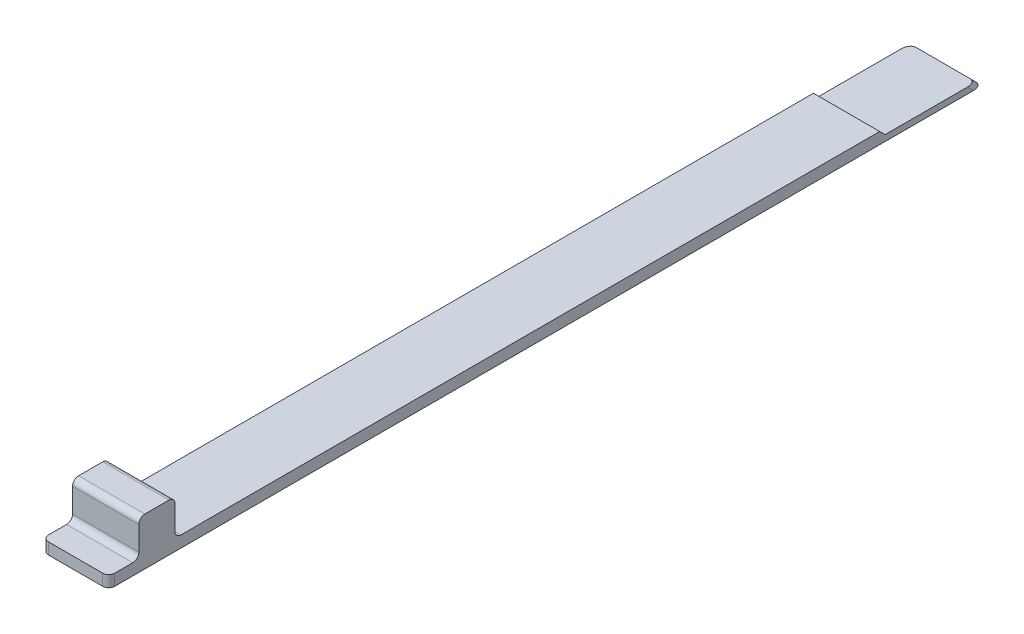
SolidWorks part; units mm, degrees
ref_plane "Front Plane" through (0, 0, 0) normal (0, 0, 1) x (1, 0, 0)
ref_plane "Top Plane" through (0, 0, 0) normal (0, 1, 0) x (1, 0, 0)
ref_plane "Right Plane" through (0, 0, 0) normal (1, 0, 0) x (0, 0, -1)
sketch "Szkic1" plane through (0, 0, 0) normal (0, 1, 0) x (1, 0, 0)
  line L0 (-5.5, -72.5) -> (5.5, 72.5) construction
  line L1 (-5.5, 72.5) -> (5.5, 72.5)
  line L2 (-5.5, 72.5) -> (-5.5, -72.5)
  line L3 (-5.5, -72.5) -> (5.5, -72.5)
  line L4 (5.5, 72.5) -> (5.5, -72.5)
  dimension "D1" = 11
  dimension "D2" = 145
extrude "Dodanie-wyciągnięcie1" add sketch "Szkic1" along normal blind 1.9
sketch "Szkic3" plane through (0, 1.9, 0) normal (0, 1, 0) x (1, 0, 0)
  line L10 (-5.5, 72.5) -> (-5.5, -72.5) construction
  line L11 (-5.5, 56.5) -> (5.5, 56.5)
  line L12 (-5.5, 56.5) -> (-5.5, 72.5)
  line L13 (-5.5, 72.5) -> (5.5, 72.5)
  line L14 (5.5, 56.5) -> (5.5, 72.5)
  line L15 (5.5, -72.5) -> (5.5, 72.5) construction
  line L16 (5.5, 72.5) -> (-5.5, 72.5) construction
  dimension "D1" = 16
extrude "Wytnij-wyciągnięcie1" cut sketch "Szkic3" against normal blind 0.9
chamfer "Sfazowanie1" distance 1 angle 45 2 edges at (0, 1.9, -56.5) (0, 1, -72.5)
sketch "Szkic2" plane through (0, 1.9, 0) normal (0, 1, 0) x (1, 0, 0)
  line L0 (-5.5, 55.5) -> (-5.5, -72.5) construction
  line L1 (-5.5, -67.5) -> (5.5, -67.5)
  line L2 (-5.5, -67.5) -> (-5.5, -61.5)
  line L3 (-5.5, -61.5) -> (5.5, -61.5)
  line L4 (5.5, -67.5) -> (5.5, -61.5)
  line L5 (5.5, -72.5) -> (5.5, 55.5) construction
  line L6 (-5.5, -72.5) -> (5.5, -72.5) construction
  dimension "D1" = 6
  dimension "D2" = 5
extrude "Dodanie-wyciągnięcie2" add sketch "Szkic2" along normal blind 6
fillet "Zaokrąglenie1" radius 1 8 edges at (0, 1.9, 61.5) (0, 7.9, 61.5) (0, 7.9, 67.5) (0, 1.9, 67.5) (-5.5, 0.95, 72.5) (5.5, 0.95, 72.5) (5.5, 0.5, -72) (-5.5, 0.5, -72)
